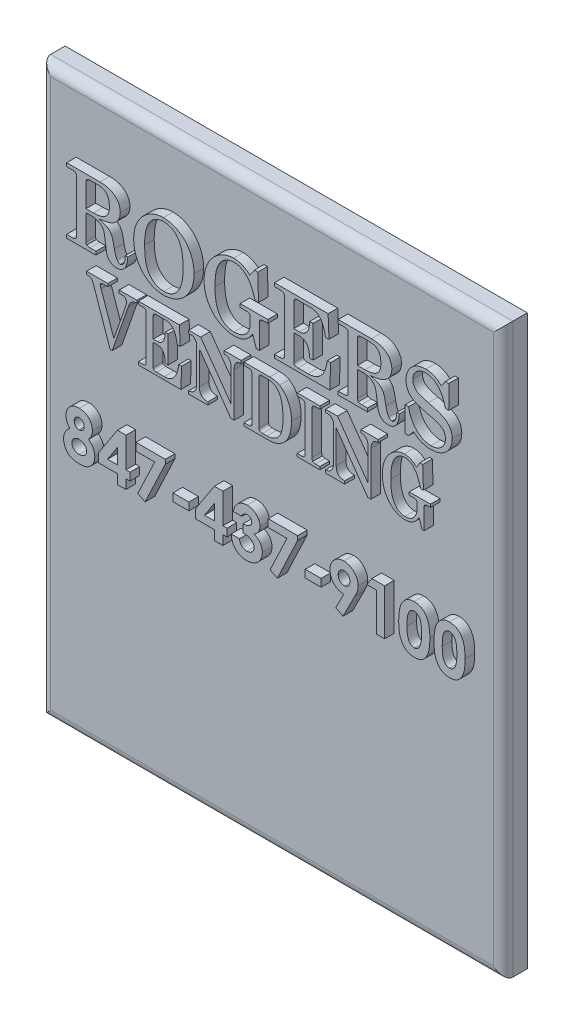
SolidWorks part; units mm, degrees
ref_plane "Front Plane" through (0, 0, 0) normal (0, 0, 1) x (1, 0, 0)
ref_plane "Top Plane" through (0, 0, 0) normal (0, 1, 0) x (1, 0, 0)
ref_plane "Right Plane" through (0, 0, 0) normal (1, 0, 0) x (0, 0, -1)
sketch "Sketch1" plane through (0, 0, 0) normal (0, 0, 1) x (1, 0, 0)
  line L1 (-27.781, 34.8285) -> (20.219, 34.8285)
  line L2 (-27.781, 34.8285) -> (-27.781, -24.1715)
  line L3 (-27.781, -24.1715) -> (20.219, -24.1715)
  line L4 (20.219, 34.8285) -> (20.219, -24.1715)
  dimension "D1" = 59
  dimension "D2" = 48
extrude "Boss-Extrude1" add sketch "Sketch1" along normal blind 2.5
ref_plane "Plane1" through (20.219, 34.8285, 2.5) normal (0, 1, 0) x (1, 0, 0)
fillet "Fillet1" radius 1 4 edges at (-3.781, -24.1715, 2.5) (-27.781, 5.3285, 2.5) (20.219, 5.3285, 2.5) (-3.781, 34.8285, 2.5)
sketch "Sketch6" plane through (0, 0, 2.5) normal (0, 0, 1) x (1, 0, 0)
  text T0 "<b>847-437-9100</b>" font "Century Gothic" height in points 18
extrude "Boss-Extrude4" add sketch "Sketch6" along normal blind 1
sketch "Sketch8" plane through (0, 0, 2.5) normal (0, 0, 1) x (1, 0, 0)
  text T0 "ROGERS" font "Century Schoolbook" height in points 26
  text T1 "VENDING" font "Century Schoolbook" height in points 22
extrude "Boss-Extrude6" add sketch "Sketch8" along normal blind 1
